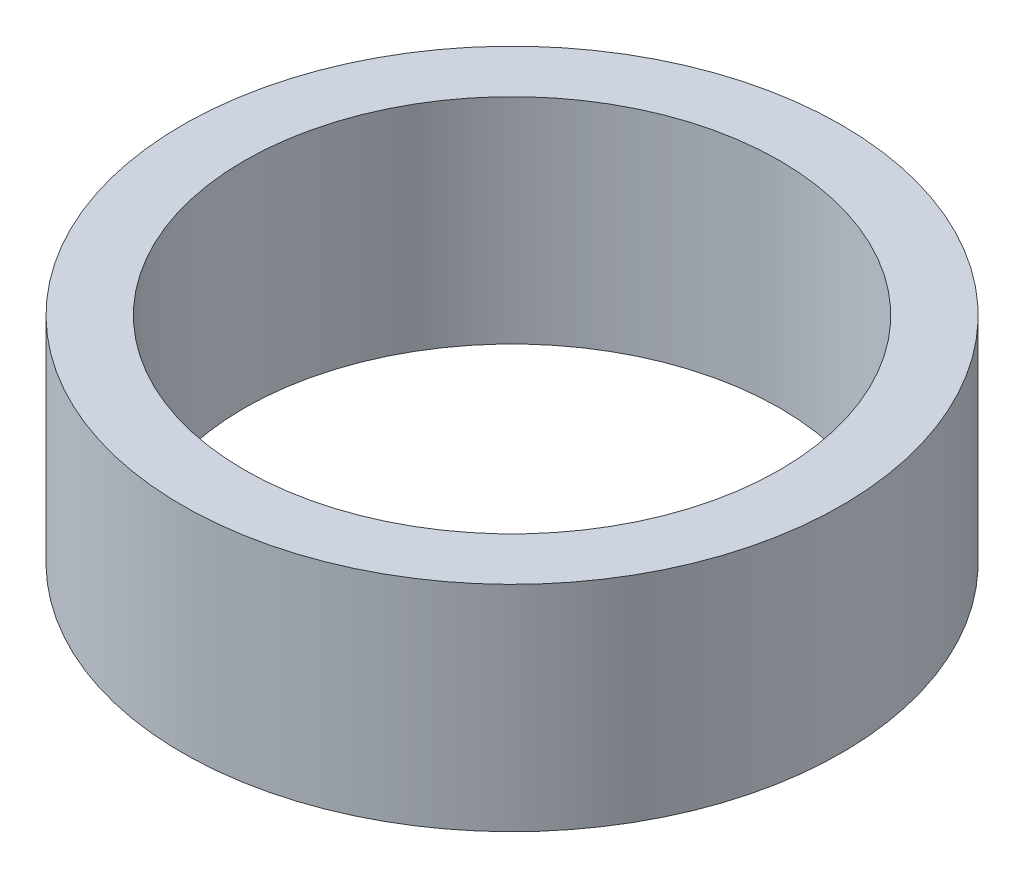
SolidWorks part; units mm, degrees
ref_plane "Front Plane" through (0, 0, 0) normal (0, 0, 1) x (1, 0, 0)
ref_plane "Top Plane" through (0, 0, 0) normal (0, 1, 0) x (1, 0, 0)
ref_plane "Right Plane" through (0, 0, 0) normal (1, 0, 0) x (0, 0, -1)
sketch "Sketch1" plane through (0, 0, 0) normal (0, 1, 0) x (1, 0, 0)
  circle A0 centre (0, 0) radius 40
  dimension "FLANGE_OD" = 80
extrude "Boss-Extrude1" add sketch "Sketch1" along normal blind 26
sketch "Sketch2" plane through (0, 0, 0) normal (0, 1, 0) x (1, 0, 0)
  circle A0 centre (0, 0) radius 32.5
  dimension "BORE_D" = 65
extrude "Cut-Extrude1" cut sketch "Sketch2" along normal through all
sketch "Sketch3" plane through (0, 26, 0) normal (0, 1, 0) x (1, 0, 0)
  circle A0 centre (0, 0) radius 17.9114 construction
  circle A1 centre (-17.9114, 0) radius 1.5
  dimension "BOLT_D" = 3
  dimension "BOLT_PCD" = 35.8227
extrude "Cut-Extrude2" cut sketch "Sketch3" against normal blind 22.8961 rebuild error yes
pattern_circular "CirPattern1" count 8 over 360 rebuild error yes
